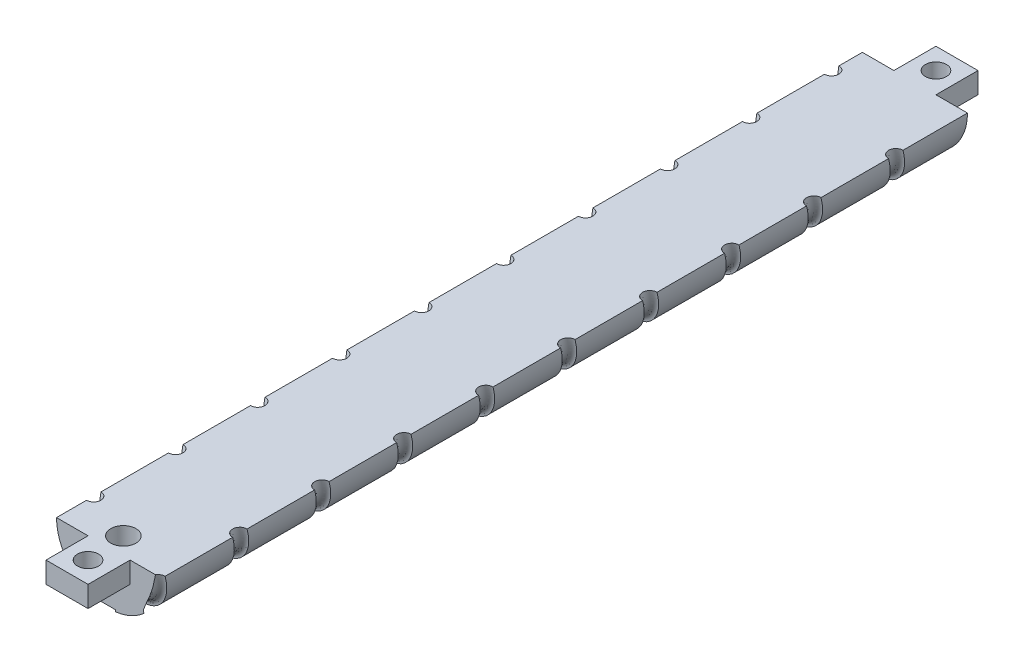
SolidWorks part; units mm, degrees
ref_plane "Alzado" through (0, 0, 0) normal (0, 0, 1) x (1, 0, 0)
ref_plane "Planta" through (0, 0, 0) normal (0, 1, 0) x (1, 0, 0)
ref_plane "Vista lateral" through (0, 0, 0) normal (1, 0, 0) x (0, 0, -1)
sketch "Croquis1" plane through (0, 0, 0) normal (0, 0, 1) x (1, 0, 0)
  line L0 (-74.1414, 30.6676) -> (-59.1414, 30.6676)
  arc A1 (-74.1414, 30.6676) -> (-59.1414, 30.6676) centre (-66.6414, 30.6676) ccw
extrude "Saliente-Extruir1" add sketch "Croquis1" along normal blind 115
sketch "Croquis4" plane through (0, 0, 0) normal (0, 0, -1) x (-1, 0, 0)
  circle A0 centre (66.6414, 30.6676) radius 7.5
curve "Hélice/Espiral1" pitch 11.7 height 117 turns 10
ref_plane "Plano1" through (-61.3381, 35.9709, 117) normal (-0.6863, 0.6863, 0.241) x (0.1704, -0.1704, 0.9705)
sketch "Croquis6" plane through (-61.3381, 35.9709, 117) normal (-0.6863, 0.6863, 0.241) x (0.1704, -0.1704, 0.9705)
  circle A0 centre (-0.0025, -0.0203) radius 1
sweep "Cortar-Barrer1" cut profiles "Croquis6" path "Hélice/Espiral1"
sketch "Croquis8" plane through (0, 0, 115) normal (0, 0, 1) x (1, 0, 0)
  line L1 (-67.7614, 23.4825) -> (-69.6987, 23.4825)
  line L2 (-69.6987, 23.4825) -> (-69.6987, 22.4148)
  line L3 (-69.6987, 22.4148) -> (-65.7472, 22.4148)
  line L4 (-65.7472, 22.4148) -> (-65.7472, 23.4825)
  line L5 (-65.7472, 23.4825) -> (-67.7614, 23.4825)
extrude "Cortar-Extruir5" cut sketch "Croquis8" against normal blind 5
sketch "Croquis9" plane through (0, 23.4825, 0) normal (0, -1, 0) x (1, 0, 0)
  circle A0 centre (-67.11, 112.4894) radius 1.8
extrude "Cortar-Extruir6" cut sketch "Croquis9" against normal blind 15
sketch "Croquis14" plane through (0, 30.6676, 0) normal (0, 1, 0) x (1, 0, 0)
  line L0 (-66.6414, 0) -> (-63.6414, 0)
  line L1 (-59.1414, 0) -> (-74.1414, 0) construction
  line L2 (-63.6414, 0) -> (-63.6414, 6)
  line L3 (-63.6414, 6) -> (-69.6414, 6)
  line L4 (-69.6414, 6) -> (-69.6414, 0)
  line L5 (-69.6414, 0) -> (-66.6414, 0)
  line L6 (-66.6414, 0) -> (-67.0794, -115) construction
  line L7 (-60.0174, -115) -> (-74.1414, -115) construction
  line L8 (-66.8604, -57.5) -> (-74.1414, -57.5) construction
  line L9 (-74.1414, -61.8553) -> (-74.1414, -52.2145) construction
  line L10 (-69.6414, -115) -> (-66.6414, -115)
  line L11 (-69.6414, -121) -> (-69.6414, -115)
  line L12 (-63.6414, -121) -> (-69.6414, -121)
  line L13 (-63.6414, -115) -> (-63.6414, -121)
  line L14 (-66.6414, -115) -> (-63.6414, -115)
  circle A0 centre (-66.6414, 3) radius 1.5
  circle A1 centre (-66.6414, -118) radius 1.5
  dimension "D1" = 6
  dimension "D3" = 3
  dimension "D2" = 6
extrude "Saliente-Extruir4" add sketch "Croquis14" against normal blind 3
